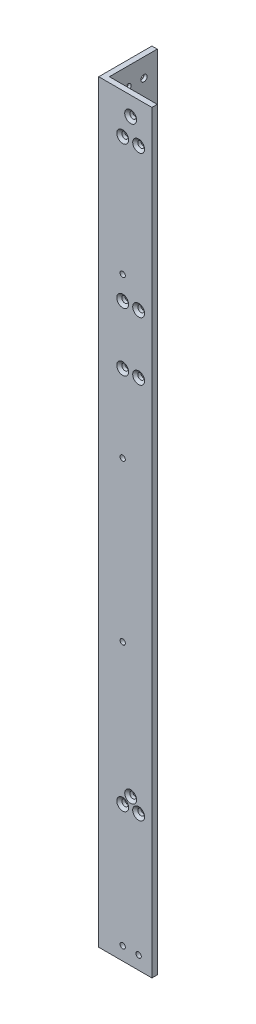
SolidWorks part; units mm, degrees
ref_plane "Front Plane" through (0, 0, 0) normal (0, 0, 1) x (1, 0, 0)
ref_plane "Top Plane" through (0, 0, 0) normal (0, 1, 0) x (1, 0, 0)
ref_plane "Right Plane" through (0, 0, 0) normal (1, 0, 0) x (0, 0, -1)
sketch "Sketch2" plane through (0, 0, 0) normal (0, 1, 0) x (1, 0, 0)
  line L0 (0, 31.75) -> (3.175, 31.75)
  line L1 (3.175, 31.75) -> (3.175, 3.175)
  line L2 (3.175, 3.175) -> (31.75, 3.175)
  line L3 (31.75, 3.175) -> (31.75, 0)
  line L4 (31.75, 0) -> (0, 0)
  line L5 (0, 0) -> (0, 31.75)
  point P9 (1.5875, 31.75)
  point P10 (31.75, 1.5875)
  dimension "D4" = 3.175
  dimension "D1" = 31.75
  dimension "D2" = 31.75
  dimension "D3" = 3.175
extrude "Boss-Extrude1" add sketch "Sketch2" along normal blind 450
sketch "RightSideHoles-Sketch3" plane through (0, 0, 0) normal (0, 0, 1) x (1, 0, 0)
  line L0 (0, 0) -> (31.75, 0) construction
  line L1 (0, 450) -> (31.75, 450) construction
  line L3 (0, 450) -> (0, 0) construction
  circle A0 centre (14.2875, 81.1125) radius 1.5875
  circle A1 centre (23.8125, 81.1125) radius 1.5875
  circle A3 centre (19.05, 87.4625) radius 1.5875
  circle A5 centre (14.2875, 426.1875) radius 1.5875
  circle A6 centre (19.05, 438.8875) radius 1.5875
  circle A7 centre (23.8125, 426.1875) radius 1.5875
  circle A8 centre (14.2875, 341.2474) radius 1.5875
  circle A9 centre (23.8125, 341.2474) radius 1.5875
  circle A10 centre (14.2875, 306.3224) radius 1.5875
  circle A11 centre (23.8125, 306.3224) radius 1.5875
  circle A12 centre (14.2875, 7.9375) radius 1.5875
  circle A13 centre (23.8125, 7.9375) radius 1.5875
  circle A14 centre (14.2875, 165) radius 1.5875
  circle A15 centre (14.2875, 260) radius 1.5875
  circle A16 centre (14.2875, 355) radius 1.5875
  dimension "D4" = 3.175
  dimension "D1" = 81.1125
  dimension "D2" = 14.2875
  dimension "D12" = 7.9375
  dimension "D7" = 34.925
  dimension "D3" = 9.525
  dimension "D10" = 341.2474
  dimension "D11" = 165
  dimension "D13" = 95
  dimension "D5" = 6.35
  dimension "D6" = 12.7
  dimension "D8" = 11.1125
  dimension "D9" = 95
  dimension "D14" = 19.05
sketch "FrontSideHoles-Sketch4" plane through (0, 0, 0) normal (-1, 0, 0) x (0, 0, 1)
  line L0 (-31.75, 450) -> (0, 450) construction
  line L1 (0, 450) -> (0, 0) construction
  line L3 (-31.75, 0) -> (0, 0) construction
  circle A0 centre (-19.05, 81.1125) radius 1.5875
  circle A2 centre (-23.8125, 87.4625) radius 1.5875
  circle A3 centre (-14.2875, 87.4625) radius 1.5875
  circle A4 centre (-23.8125, 438.8875) radius 1.5875
  circle A5 centre (-14.2875, 438.8875) radius 1.5875
  circle A6 centre (-19.05, 426.1875) radius 1.5875
  circle A8 centre (-14.2875, 354.1849) radius 2
  circle A9 centre (-14.2875, 313.9849) radius 2
  circle A10 centre (-14.2875, 165) radius 1.5875
  circle A11 centre (-14.2875, 260) radius 1.5875
  circle A13 centre (-23.8125, 7.9375) radius 1.5875
  circle A14 centre (-14.2875, 7.9375) radius 1.5875
  dimension "D4" = 3.175
  dimension "D13" = 95
  dimension "D5" = 6.35
  dimension "D16" = 4
  dimension "D6" = 11.1125
  dimension "D9" = 40.2
  dimension "D10" = 14.2875
  dimension "D7" = 12.7
  dimension "D12" = 165
  dimension "D15" = 7.9375
  dimension "D2" = 14.2875
  dimension "D11" = 9.525
  dimension "D3" = 81.1125
  dimension "D8" = 354.1849
  dimension "D14" = 19.05
extrude "RightSideHoles-Cut-Extrude1" cut sketch "RightSideHoles-Sketch3" against normal blind 3.175
extrude "FrontSideHoles-Cut-Extrude2" cut sketch "FrontSideHoles-Sketch4" against normal blind 3.175
sketch "Sketch5" plane through (0, 0, 0) normal (-1, 0, 0) x (0, 0, 1)
  point P0 (-23.8125, 438.8875)
  point P3 (-19.05, 426.1875)
  point P6 (-14.2875, 438.8875)
  point P9 (-19.05, 81.1125)
  point P12 (-14.2875, 87.4625)
  point P15 (-23.8125, 87.4625)
hole_wizard "CSK for #6 Flat Head Machine Screw (100)2" positions "Sketch5" profile "Sketch6" countersink size "#6" standard "ANSI Inch" end condition through all
sketch "Sketch6" plane through (0, 438.8875, -23.8125) normal (0, 1, 0) x (0, 0, 1)
  line L0 (0, 0) -> (0, 31.75)
  line L1 (0, 31.75) -> (1.8986, 31.75)
  line L2 (1.8986, 31.75) -> (1.8986, 1.38)
  line L3 (1.8986, 1.38) -> (3.5433, 0)
  line L5 (3.5433, 0) -> (0, 0)
  line L6 (-1.8986, 1.38) -> (-3.5433, 0) construction
  line L11 (0, -6.35) -> (0, 107.95) construction
  dimension "Thru Hole Dia." = 3.7973
  dimension "Thru Hole Depth" = 31.75
  dimension "Near C'Sink Dia." = 7.0866
  dimension "Near C'Sink Angle" = 100
sketch "Sketch11" plane through (0, 0, 0) normal (0, 0, 1) x (1, 0, 0)
  point P0 (14.2875, 81.1125)
  point P3 (19.05, 87.4625)
  point P6 (23.8125, 81.1125)
  point P9 (14.2875, 306.3224)
  point P12 (23.8125, 306.3224)
  point P15 (14.2875, 341.2474)
  point P18 (23.8125, 341.2474)
  point P21 (14.2875, 426.1875)
  point P24 (23.8125, 426.1875)
  point P27 (19.05, 438.8875)
hole_wizard "CSK for #6 Flat Head Machine Screw (100)3" positions "Sketch11" profile "Sketch12" countersink size "#6" standard "ANSI Inch" end condition through all
sketch "Sketch12" plane through (14.2875, 81.1125, 0) normal (1, 0, 0) x (0, -1, 0)
  line L0 (0, 0) -> (0, 31.75)
  line L1 (0, 31.75) -> (1.8986, 31.75)
  line L2 (1.8986, 31.75) -> (1.8986, 1.38)
  line L3 (1.8986, 1.38) -> (3.5433, 0)
  line L5 (3.5433, 0) -> (0, 0)
  line L6 (-1.8986, 1.38) -> (-3.5433, 0) construction
  line L11 (0, -6.35) -> (0, 107.95) construction
  dimension "Thru Hole Dia." = 3.7973
  dimension "Thru Hole Depth" = 31.75
  dimension "Near C'Sink Dia." = 7.0866
  dimension "Near C'Sink Angle" = 100
equation "\"RailThickness\"= .125in'Spec"
equation "\"VSWidth\"= 1.25in'Spec"
equation "\"VSHeight\"= 1.25in'Spec"
equation "\"VSLength\"= 450mm"
equation "\"HoleOffsetFromEdge\"= \"RailThickness\" * 2.5"
equation "\"HoleOffsetFromSide\"= \"RailThickness\" * 3.5"
equation "\"LegHeight\"= 70mm'Space needed for PSU/Stepper/Electronics"
equation "\"VSBottomSideRailHoleY1FromBottomOfLowerRail\"= \"V1 BottomOfLowerRail\" + \"HoleOffsetFromSide\"'Equals 81.1125"
equation "\"VSSideRailHoleX1FromSide\"= \"HoleOffsetFromSide\" + \"RailThickness\""
equation "\"FasteningHoleDiameter\"= .125in"
equation "\"VSBottomSideRailHoleY2FromY1\"= \"LowerRailHeight\" - \"HoleOffsetFromSide\" - \"HoleOffsetFromEdge\"'Equals 6.35"
equation "\"VSTopSideRailHoleY1FromEdge\"= \"HoleOffsetFromEdge\" + \"RailThickness\""
equation "\"D4@RightSideHoles-Sketch3\" = \"FasteningHoleDiameter\""
equation "\"D1@RightSideHoles-Sketch3\" = \"VSBottomSideRailHoleY1FromBottomOfLowerRail\""
equation "\"D2@RightSideHoles-Sketch3\" = \"VSSideRailHoleX1FromSide\""
equation "\"D1@Boss-Extrude1\"=\"VSLength\""
equation "\"D4@FrontSideHoles-Sketch4\" = \"FasteningHoleDiameter\""
equation "\"D6@FrontSideHoles-Sketch4\" = \"VSTopSideRailHoleY1FromEdge\""
equation "\"VSMidSideRailHoleY1FromV8TopOfMidSideRail\"= \"V8 ToTopOfMidSideRail\" - \"HoleOffsetFromEdge\"'Equals 341.24737"
equation "\"LowerRailHeight\"= 1.00in"
equation "\"D2@Sketch2\"=\"VSWidth\""
equation "\"D1@Sketch2\"=\"VSHeight\""
equation "\"TopRailHeight\"= 1.25in"
equation "\"MidLeftOrRightSideRailHeight\"= 2.0in"
equation "\"D12@RightSideHoles-Sketch3\"=\"HoleOffsetFromEdge\""
equation "\"VSMidSideRailHoleY2FromY1\"= \"MidLeftOrRightSideRailHeight\" - \"HoleOffsetFromEdge\" * 2'Equals 34.925"
equation "\"D7@RightSideHoles-Sketch3\"=\"VSMidSideRailHoleY2FromY1\""
equation "\"VSTopSideRailHoleY2FromY1\"= \"TopRailHeight\" - \"VSTopSideRailHoleY1FromEdge\" - \"HoleOffsetFromEdge\"'Equals 12.7"
equation "\"D7@FrontSideHoles-Sketch4\"=\"VSTopSideRailHoleY2FromY1\""
equation "\"VSSideRailHoleX2FromX1\"= \"VSWidth\" - \"VSSideRailHoleX1FromSide\" - \"HoleOffsetFromEdge\""
equation "\"D3@RightSideHoles-Sketch3\"=\"VSSideRailHoleX2FromX1\""
equation "\"1mmSpacer\"= 1mm"
equation "\"20TGT2PulleyWidth\"= 8.7mm'The STL of the Pulley in the diagram is a bit larger"
equation "\"BeltTensionerInnerHeight\"= \"20TGT2PulleyWidth\" * 2 + \"1mmSpacer\" * 3"
equation "\"BeltTensionerHeight\"= 60mm"
equation "\"D9@FrontSideHoles-Sketch4\"=\"VSBeltTensionerHoleY2FromY1\""
equation "\"VSBeltTensionerHoleY1ToAlignedWithYAxisGantryBlockUpperPulley\"= \"V5 ToBottomOfXAxisLinearRail\" - \"DistanceFromXAxisLinearRailBottomAndTopGantryPulley\" + \"DistanceFromBeltTensionerTopPulleyToBeltTensionerTop\" - \"BeltTensionerMountingHoleOffsetFromTopOrBottom\"'Equals 354.18487"
equation "\"VSBeltTensionerHoleY2FromY1\"= \"BeltTensionerHeight\" - \"BeltTensionerMountingHoleOffsetFromTopOrBottom\" * 2"
equation "\"V1 BottomOfLowerRail\"= \"LegHeight\""
equation "\"StepperShaftLength\"= 24mm'Pulley will be attached to the end"
equation "\"ZAxisLeadScrewLength\"= 200mm"
equation "\"LM8UUHeight\"= 24mm'Spec"
equation "\"V2 ToBedAtTopOfZAxis\"= \"V1 BottomOfLowerRail\" - \"LowerEnclosureThickness\" + \"StepperShaftLength\" + \"ZAxisLeadScrewLength\" - \"LM8UUHeight\" / 2'Equals 277"
equation "\"HotEndToTopOfXAxisGB\"= 71.68487mm'Equals 71.68487. Measured after installed onto X-Axis linear rail guide block"
equation "\"TopOfGBToBottomOfLinearRail\"= \"LinearGBWidth\" / 2 + \"LinearRailWidth\" / 2'Equals 19.5"
equation "\"LinearGBWidth\"= 27mm'Spec"
equation "\"V5 ToBottomOfXAxisLinearRail\"= \"V4 ToTopOfBuildPlate/HotEndTip\" + \"HotEndToTopOfXAxisGB\" - \"TopOfGBToBottomOfLinearRail\"'Equals 352.18487"
equation "\"LinearRailWidth\"= 12mm'Spec"
equation "\"V6 ToMiddleOfYAxisGantryBlock\"= \"V5 ToBottomOfXAxisLinearRail\" - \"GABHeight\" / 2'Equals 334.18487"
equation "\"GABUpperHeight\"= 4mm"
equation "\"GABMidWallHeight\"= 28mm'Must equal 28 or changes alignment"
equation "\"D10@RightSideHoles-Sketch3\"=\"VSMidSideRailHoleY1FromV8TopOfMidSideRail\""
equation "\"BedToBuildPlateStandoffLength\"= 15mm"
equation "\"BuildPlateHeight\"= 8mm'Spec"
equation "\"V4 ToTopOfBuildPlate/HotEndTip\"= \"V2 ToBedAtTopOfZAxis\" + \"BedToBuildPlateStandoffLength\" + \"BuildPlateHeight\""
equation "\"V8 ToTopOfMidSideRail\"= \"V6 ToMiddleOfYAxisGantryBlock\" + \"MidSideRailVerticalOffset\"'Equals 349.18487"
equation "\"BeltTensionerMountingHoleOffsetFromEdge\"= \"HoleOffsetFromEdge\""
equation "\"VSBeltTensionerXMountingHoleOffsetFromSide\"= \"BeltTensionerMountingHoleOffsetFromEdge\" + \"RailThickness\" * 2"
equation "\"D10@FrontSideHoles-Sketch4\"=\"VSBeltTensionerXMountingHoleOffsetFromSide\""
equation "\"VSEnclosureOffsets\"= ( \"VSLength\" - \"LegHeight\" ) / 4"
equation "\"D11@RightSideHoles-Sketch3\"=\"LegHeight\" + \"VSEnclosureOffsets\""
equation "\"D13@RightSideHoles-Sketch3\"=\"VSEnclosureOffsets\""
equation "\"D12@FrontSideHoles-Sketch4\"= \"LegHeight\" + \"VSEnclosureOffsets\""
equation "\"D13@FrontSideHoles-Sketch4\"=\"VSEnclosureOffsets\""
equation "\"D15@FrontSideHoles-Sketch4\"=\"HoleOffsetFromEdge\""
equation "\"D2@FrontSideHoles-Sketch4\"=\"VSSideRailHoleX1FromSide\""
equation "\"D5@FrontSideHoles-Sketch4\"=\"VSBottomSideRailHoleY2FromY1\""
equation "\"D3@FrontSideHoles-Sketch4\"=\"VSBottomSideRailHoleY1FromBottomOfLowerRail\""
equation "\"D5@RightSideHoles-Sketch3\"=\"VSBottomSideRailHoleY2FromY1\""
equation "\"D6@RightSideHoles-Sketch3\"=\"VSTopSideRailHoleY2FromY1\""
equation "\"D8@RightSideHoles-Sketch3\"=\"VSTopSideRailHoleY1FromEdge\""
equation "\"BeltTensionerMountingHoleDiameter\"= 4.0mm"
equation "\"D16@FrontSideHoles-Sketch4\"=\"BeltTensionerMountingHoleDiameter\""
equation "\"LowerEnclosureThickness\"= 5mm"
equation "\"GABLowerHeight\"= 4mm"
equation "\"GABHeight\"= \"GABLowerHeight\" + \"GABMidWallHeight\" + \"GABUpperHeight\""
equation "\"D9@RightSideHoles-Sketch3\"=\"VSEnclosureOffsets\""
equation "\"BeltTensionerMountingHoleOffsetFromTopOrBottom\"= ( \"BeltTensionerHeight\" - \"BeltTensionerInnerHeight\" ) / 4"
equation "\"MidSideRailVerticalOffset\"= \"LinearRailWidth\" + 3mm'Allows space for RodStabilizer to attach to bottom of MidSideRail"
equation "\"GABRiserBossOffset\"= 0.4mm'Aligns Pulleys inside edges to be 2.5mm (.5mm apart top to bottom)"
equation "\"GABMidShortRiserHeight\"= \"GABMidWallHeight\" / 2 - \"20TGT2PulleyWidth\"'Equals 5.3"
equation "\"7mmx1mmSpacerHeight\"= 1mm"
equation "\"D8@FrontSideHoles-Sketch4\"=\"VSBeltTensionerHoleY1ToAlignedWithYAxisGantryBlockUpperPulley\""
equation "\"DistanceFromXAxisLinearRailBottomAndTopGantryPulley\"= \"GABUpperHeight\" + \"GABMidShortRiserHeight\" - \"GABRiserBossOffset\"'Equals 8.9"
equation "\"DistanceFromBeltTensionerTopPulleyToBeltTensionerTop\"= \"7mmx1mmSpacerHeight\" + \"BeltTensionerTopHeight\"'Equals 20.8"
equation "\"BeltTensionerTopHeight\"= ( \"BeltTensionerHeight\" - \"BeltTensionerInnerHeight\" ) / 2'Equals 19.8"
equation "\"D14@RightSideHoles-Sketch3\"=\"VSMidSideRailHoleXFromSideToCenter\""
equation "\"VSMidSideRailHoleXFromSideToCenter\"= \"RailThickness\" * 6"
equation "\"D14@FrontSideHoles-Sketch4\"=\"VSMidSideRailHoleXFromSideToCenter\""
equation "\"D11@FrontSideHoles-Sketch4\"=\"VSSideRailHoleX2FromX1\""
